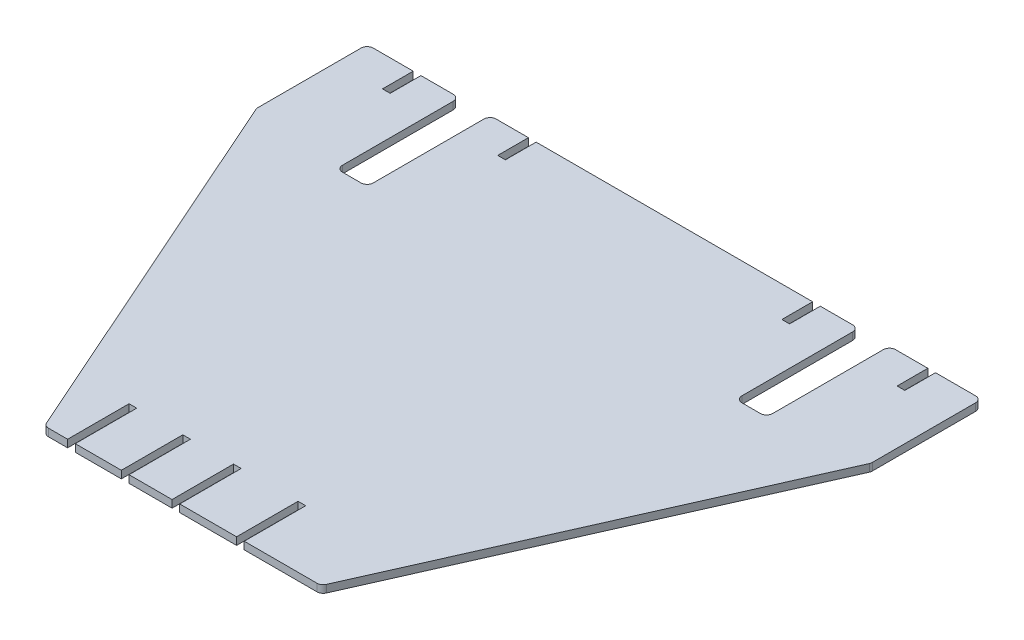
SolidWorks part; units mm, degrees
material "Corrugated Paper"
ref_plane "Front Plane" through (0, 0, 0) normal (0, 0, 1) x (1, 0, 0)
ref_plane "Top Plane" through (0, 0, 0) normal (0, 1, 0) x (1, 0, 0)
ref_plane "Right Plane" through (0, 0, 0) normal (1, 0, 0) x (0, 0, -1)
sketch "Sketch1" plane through (0, 0, 0) normal (0, 1, 0) x (1, 0, 0)
  line L0 (0, 0) -> (0, -142.875) construction
  line L3 (3.3512, -101.6) -> (-1.27, -101.6)
  line L4 (-57.15, -101.6) -> (-127, 55.88)
  line L5 (-127, 55.88) -> (-127, 101.6)
  line L6 (-127, 101.6) -> (-107.95, 101.6)
  line L7 (-88.9, 101.6) -> (-88.9, 50.8)
  line L9 (-88.9, 50.8) -> (-76.2, 50.8)
  line L10 (-76.2, 50.8) -> (-76.2, 101.6)
  line L11 (-76.2, 101.6) -> (-60.325, 101.6)
  line L13 (76.2, 50.8) -> (76.2, 101.6)
  line L14 (88.9, 50.8) -> (76.2, 50.8)
  line L15 (88.9, 101.6) -> (88.9, 50.8)
  line L16 (127, 101.6) -> (107.95, 101.6)
  line L17 (127, 55.88) -> (127, 101.6)
  line L18 (57.15, -101.6) -> (127, 55.88)
  line L19 (3.3512, -101.6) -> (22.225, -101.6)
  line L21 (-127, 101.6) -> (127, -101.6) construction
  line L22 (-25.4, -101.6) -> (-44.45, -101.6)
  line L24 (-25.4, -101.6) -> (-25.4, -76.2)
  line L25 (-25.4, -76.2) -> (-22.225, -76.2)
  line L26 (-22.225, -101.6) -> (-22.225, -76.2)
  line L27 (25.4, -101.6) -> (25.4, -76.2)
  line L28 (25.4, -76.2) -> (22.225, -76.2)
  line L29 (22.225, -101.6) -> (22.225, -76.2)
  line L30 (25.4, -101.6) -> (57.15, -101.6)
  line L31 (-82.55, 50.8) -> (-82.55, 101.6) construction
  line L32 (-104.775, 101.6) -> (-88.9, 101.6)
  line L34 (-107.95, 101.6) -> (-107.95, 88.9)
  line L35 (-107.95, 88.9) -> (-104.775, 88.9)
  line L36 (-104.775, 101.6) -> (-104.775, 88.9)
  line L37 (-57.15, 101.6) -> (-57.15, 88.9)
  line L38 (-57.15, 88.9) -> (-60.325, 88.9)
  line L39 (-60.325, 101.6) -> (-60.325, 88.9)
  line L40 (-57.15, 101.6) -> (57.15, 101.6)
  line L41 (107.95, 101.6) -> (107.95, 88.9)
  line L42 (107.95, 88.9) -> (104.775, 88.9)
  line L43 (104.775, 101.6) -> (104.775, 88.9)
  line L44 (57.15, 101.6) -> (57.15, 88.9)
  line L45 (60.325, 101.6) -> (60.325, 88.9)
  line L46 (57.15, 88.9) -> (60.325, 88.9)
  line L47 (60.325, 101.6) -> (76.2, 101.6)
  line L48 (104.775, 101.6) -> (88.9, 101.6)
  line L49 (-47.625, -101.6) -> (-47.625, -76.2)
  line L50 (-47.625, -76.2) -> (-44.45, -76.2)
  line L51 (-44.45, -76.2) -> (-44.45, -101.6)
  line L52 (-47.625, -101.6) -> (-57.15, -101.6)
  line L53 (-4.445, -101.6) -> (-4.445, -76.2)
  line L54 (-4.445, -76.2) -> (-1.27, -76.2)
  line L55 (-1.27, -76.2) -> (-1.27, -101.6)
  line L56 (-4.445, -101.6) -> (-22.225, -101.6)
  dimension "D3" = 254
  dimension "D6" = 50.8
  dimension "D7" = 203.2
  dimension "D8" = 45.72
  dimension "D10" = 3.175
  dimension "D11" = 25.4
  dimension "D12" = 3.175
  dimension "D4" = 114.3
  dimension "D13" = 50.8
  dimension "D9" = 50.8
  dimension "D14" = 38.1
  dimension "D15" = 12.7
  dimension "D16" = 19.05
  dimension "D2" = 24.13
  dimension "D5" = 12.7
extrude "Boss-Extrude1" add sketch "Sketch1" along normal blind 3.0988 contours L13 L47 L45 L46 L44 L40 L37 L38 L39 L11 L10 L9 L7 L32 L36 L35 L34 L6 L5 L4 L52 L49 L50 L51 L22 L24 L25 L26 L56 L53 L54 L55 L3 L19 L29 L28 L27 L30 L18 L17 L16 L41 L42 L43 L48 L15 L14
fillet "Fillet1" radius 2.54 14 edges at (88.9, 1.5494, -50.8) (88.9, 1.5494, -101.6) (-127, 1.5494, -55.88) (-127, 1.5494, -101.6) (-88.9, 1.5494, -101.6) (-88.9, 1.5494, -50.8) (-76.2, 1.5494, -50.8) (-76.2, 1.5494, -101.6) (76.2, 1.5494, -101.6) (76.2, 1.5494, -50.8) (127, 1.5494, -101.6) (127, 1.5494, -55.88) (57.15, 1.5494, 101.6) (-57.15, 1.5494, 101.6)
sketch "Sketch4" plane through (0, 3.0988, 0) normal (0, 1, 0) x (1, 0, 0)
  line L0 (0, -164.31) -> (0, 101.6) construction
  line L1 (-63.105, 101.6) -> (63.105, 101.6) construction
  line L2 (-63.105, 101.6) -> (-63.105, -164.31) construction
  line L3 (-63.105, -164.31) -> (63.105, -164.31) construction
  line L4 (63.105, 101.6) -> (63.105, -164.31) construction
  line L5 (57.8198, -100.0899) -> (126.7819, 55.3882) construction
  line L6 (65.3301, -83.1577) -> (50.405, -83.1577)
  line L7 (65.3301, -83.1577) -> (65.3301, -88.1742)
  line L8 (65.3301, -88.1742) -> (50.405, -88.1742)
  line L9 (50.405, -83.1577) -> (50.405, -88.1742)
  line L10 (-50.405, -83.1577) -> (-50.405, -88.1742)
  line L11 (-65.3301, -88.1742) -> (-50.405, -88.1742)
  line L12 (-65.3301, -83.1577) -> (-65.3301, -88.1742)
  line L13 (-65.3301, -83.1577) -> (-50.405, -83.1577)
  line L14 (-57.15, 101.6) -> (57.15, 101.6) construction
  line L15 (-1.5875, 101.6) -> (1.5875, 101.6)
  line L16 (-1.5875, 101.6) -> (-1.5875, 88.9)
  line L17 (-1.5875, 88.9) -> (1.5875, 88.9)
  line L18 (1.5875, 101.6) -> (1.5875, 88.9)
  point P8 (63.105, -88.1742)
  point P11 (0, 101.6)
  dimension "D1" = 265.91
  dimension "D2" = 126.21
  dimension "D5" = 3.175
  dimension "D6" = 12.7
  dimension "D4" = 12.7
  dimension "D3" = 5.0165
extrude "Cut-Extrude3" [suppressed] cut sketch "Sketch4" against normal through all
equation "\"D1@Boss-Extrude1\" = \"thick\""
equation "\"D10@Sketch1\"=\"thick\"+\"clear\""
equation "\"D12@Sketch1\"=\"thick\"+\"clear\""
equation "\"rodThick\"= 0.085in"
equation "\"thick\"= 0.122in"
equation "\"clear\"= 0.003in"
equation "\"D5@Sketch4\"=\"thick\"+\"clear\""
